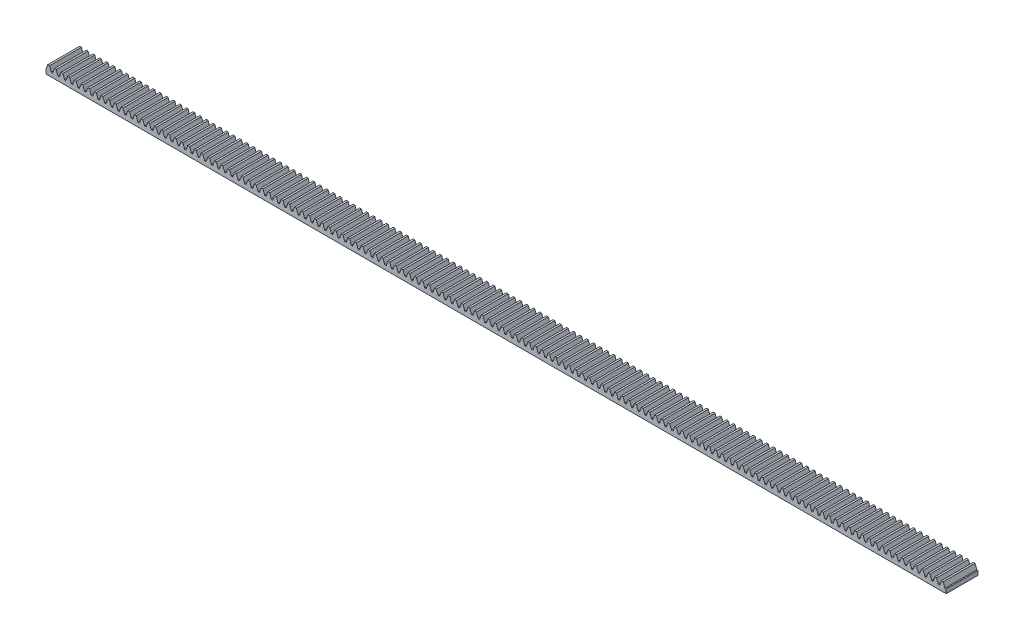
SolidWorks part; units mm, degrees
ref_plane "前视基准面" through (0, 0, 0) normal (0, 0, 1) x (1, 0, 0)
ref_plane "上视基准面" through (0, 0, 0) normal (0, 1, 0) x (1, 0, 0)
ref_plane "右视基准面" through (0, 0, 0) normal (1, 0, 0) x (0, 0, -1)
sketch "草图1" plane through (0, 0, 0) normal (0, 0, 1) x (1, 0, 0)
  line L1 (0, 0) -> (424, 0)
  line L2 (0, 0) -> (0, -2)
  line L3 (0, -2) -> (424, -2)
  line L4 (424, 0) -> (424, -2)
  dimension "D1" = 2
  dimension "L" = 424
extrude "拉伸1" add sketch "草图1" along normal blind 15
sketch "草图2" plane through (0, 0, 15) normal (0, 0, 1) x (1, 0, 0)
  line L0 (0, 0) -> (0.8189, 2.25)
  line L1 (0.8189, 2.25) -> (1.6618, 2.25)
  line L2 (1.6618, 2.25) -> (2.4807, 0)
  line L3 (424, 0) -> (0, 0) construction
  line L4 (0, 0) -> (2.4807, 0)
  line L5 (0.455, 1.25) -> (2.0258, 1.25) construction
  dimension "D2" = 70
  dimension "alpha" = 110
  dimension "ha" = 1
  dimension "hf" = 1.25
  dimension "S" = 1.5708
extrude "拉伸2" add sketch "草图2" against normal up to surface (15 mm away) up to face at (212, -1, 0)
pattern_linear "阵列(线性)3" count 135 spacing 3.1416 along (1, 0, 0) of "拉伸2"
sketch "草图3" plane through (0, 0, 15) normal (0, 0, 1) x (1, 0, 0)
  line L0 (1.6618, 2.25) -> (0.8189, 2.25) construction
  line L1 (0, 0) -> (3.1416, 0)
  line L2 (0, 0) -> (0, 2.25)
  line L3 (0, 2.25) -> (3.1416, 2.25)
  line L4 (3.1416, 0) -> (3.1416, 2.25)
  line L5 (318.9626, 2.25) -> (318.1198, 2.25) construction
  line L6 (424, 0) -> (316.64, 0)
  line L7 (424, 0) -> (424, 2.25)
  line L8 (424, 2.25) -> (316.64, 2.25)
  line L9 (316.64, 0) -> (316.64, 2.25)
sketch "草图4" plane through (0, 0, 0) normal (-1, 0, 0) x (0, 0, 1)
  line L0 (0, -2) -> (15, -2)
  line L1 (15, -2) -> (15, 2.25)
  line L2 (15, 2.25) -> (0, 2.25)
  line L3 (0, 0) -> (0, 2.25) construction
  line L4 (0, 2.25) -> (15, 2.25) construction
  line L5 (0, 2.25) -> (0, -2)
extrude "切除-拉伸1" [suppressed] cut sketch "草图4" against normal blind 15
equation "\"d\"= \"S@草图2\" * 2"
equation "\"z\"= 0.5"
